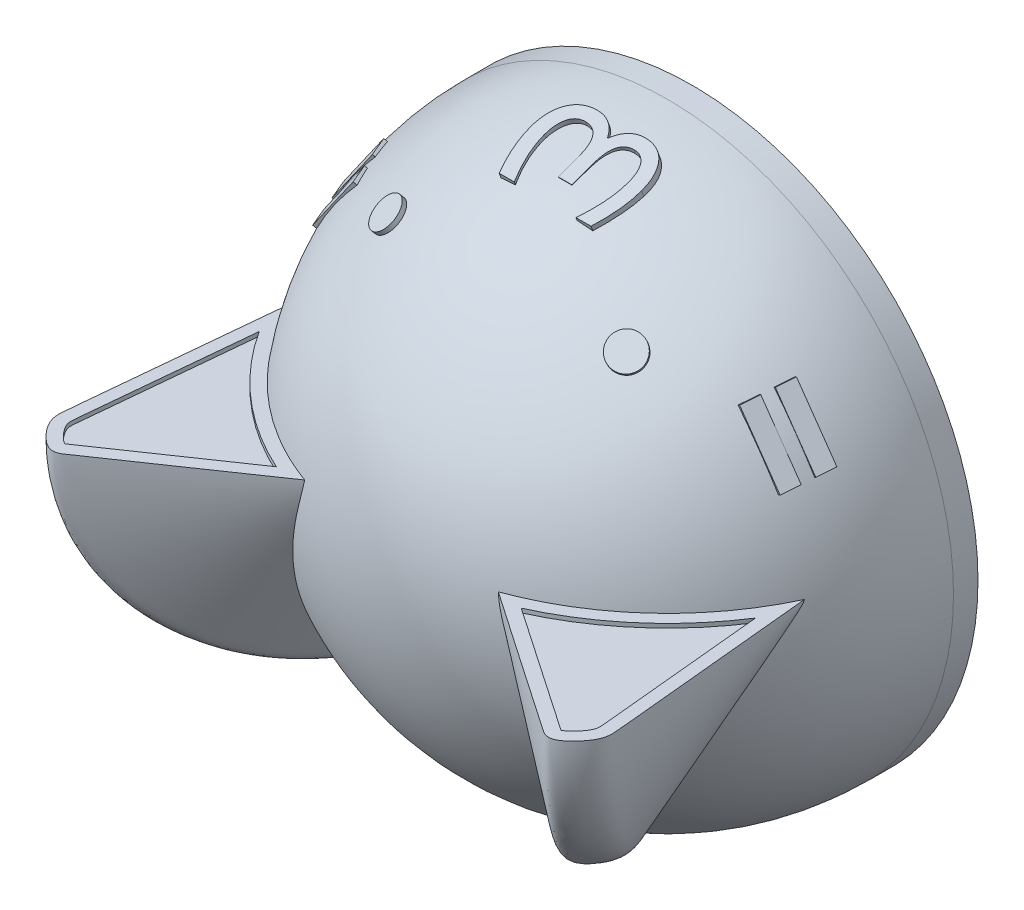
SolidWorks part; units mm, degrees
ref_plane "Front Plane" through (0, 0, 0) normal (0, 0, 1) x (1, 0, 0)
ref_plane "Top Plane" through (0, 0, 0) normal (0, 1, 0) x (1, 0, 0)
ref_plane "Right Plane" through (0, 0, 0) normal (1, 0, 0) x (0, 0, -1)
sketch "Sketch2" plane through (0, 0, 0) normal (0, 0, 1) x (1, 0, 0)
  circle A0 centre (0, 0) radius 70
  dimension "D1" = 140
sketch "Sketch1" plane through (0, 0, 0) normal (0, 0, 1) x (1, 0, 0)
  line L8 (48.8765, 46.4076) -> (-48.8765, 46.4076)
  line L9 (-48.8765, 46.4076) -> (-48.8765, -28.5347)
  line L10 (-48.8765, -28.5347) -> (48.8765, -28.5347)
  line L11 (48.8765, -28.5347) -> (48.8765, 46.4076)
  line L12 (48.8765, 46.4076) -> (-48.8765, 46.4076)
  line L13 (-48.8765, 46.4076) -> (-48.8765, -28.5347)
  line L14 (-48.8765, -28.5347) -> (48.8765, -28.5347)
  line L15 (48.8765, -28.5347) -> (48.8765, 46.4076)
  dimension "D2" = 2.75
extrude "Boss-Extrude1" add sketch "Sketch2" along normal blind 6
extrude "Cut-Extrude1" cut sketch "Sketch1" along normal blind 5
dome "Dome1" faces to dome 1 distance 70 reverse direction no elliptical dome no face at (70, 0, 6) parameters "D1"=70
ref_plane "Plane1" through (0, 10, 0) normal (0, 1, 0) x (1, 0, 0)
sketch "Sketch6" plane through (0, 10, 0) normal (0, 1, 0) x (1, 0, 0)
  line L0 (-62.7908, -35.2799) -> (-69.282, -102.407) construction
  line L2 (70, -6) -> (-70, -6) construction
  line L3 (-69.282, -102.407) -> (-23.6959, -71.1038) construction
  line L4 (-62.7908, -35.2799) -> (0, -6) construction
  line L5 (0, -6) -> (-23.6959, -71.1038) construction
  line L6 (0, -6) -> (0, 0) construction
  arc A0 (-69.282, -6) -> (69.282, -6) centre (0, -6) ccw
  arc A1 (-69.282, -6) -> (69.282, -6) centre (0, -6) ccw construction
  arc A2 (-62.7908, -35.2799) -> (-23.6959, -71.1038) centre (0, -6) ccw
  spline S0 degree 3 poles (-62.7908, -35.2799) (-64.4136, -52.0616) (-66.0364, -68.8434) (-67.6592, -85.6252) (-67.801, -87.0913) (-68.0846, -90.0236) (-61.5282, -97.0826) (-59.0997, -95.415) (-57.8855, -94.5812) (-46.4889, -86.7554) (-35.0924, -78.9296) (-23.6959, -71.1038) knots 0 0 0 0 0.480293 0.480293 0.480293 0.522253 0.564213 0.606173 0.606173 0.606173 1 1 1 1
  dimension "D2" = 50
  dimension "D3" = 20
  dimension "D4" = 45
ref_axis "Axis1" through (-69.282, 10, 102.407) along (0.5836, 0, -0.8121)
ref_plane "Plane2" through (2.8434, 0, 2.0434) normal (0.8121, 0, 0.5836) x (0.3406, -0.8121, -0.4739)
sketch "Sketch7" plane through (2.8434, 0, 2.0434) normal (0.8121, 0, 0.5836) x (0.3406, -0.8121, -0.4739)
  line L0 (-46.2239, -47.1856) -> (-74.5562, -86.6104) construction
  line L1 (-46.2239, -47.1856) -> (-74.5562, -86.6104) construction
  line L2 (12.6309, 34.7118) -> (-51.3954, -54.3818) construction
  line L3 (-46.2239, -47.1856) -> (-74.5562, -86.6104) construction
  arc A0 (-59.6874, 36.8938) -> (54.0006, -44.8071) centre (-2.8434, -3.9566) ccw
  arc A1 (-59.6874, 36.8938) -> (54.0006, -44.8071) centre (-2.8434, -3.9566) ccw construction
  arc A2 (-74.5562, -86.6104) -> (-3.9128, -73.9485) centre (-45.3773, -46.0075) ccw
  arc A3 (-59.6874, 36.8938) -> (54.0006, -44.8071) centre (-2.8434, -3.9566) ccw construction
  dimension "D1" = 50
sweep "Sweep1" add profiles "Sketch6" path "Sketch7"
mirror "Mirror1" about plane through (0, 0, 0) normal (1, 0, 0) of "Sweep1"
sketch "Sketch8" plane through (0, 10, 0) normal (0, 1, 0) x (1, 0, 0)
  line L0 (-60.7052, -92.783) -> (-29.9727, -71.7748)
  arc A2 (-60.7352, -45.1908) -> (-29.9727, -71.7748) centre (0, -6) ccw
  arc A3 (-60.7352, -45.1908) -> (-29.9727, -71.7748) centre (0, -6) ccw
  spline S2 degree 3 poles (228.0161, 2940.8674) (130.9731, 1937.3188) (33.5339, 929.6722) (-64.0045, -78.9989) (-64.5246, -84.3774) (-64.6484, -85.658) (-64.6979, -86.1702) (-64.7231, -86.4263) (-64.7569, -86.9394) (-64.7656, -87.1964) (-64.7356, -87.7127) (-64.6944, -87.9682) (-64.4849, -88.7007) (-64.2349, -89.1595) (-63.6777, -90.016) (-63.3673, -90.4201) (-62.7014, -91.1945) (-62.3441, -91.5657) (-61.7717, -92.0782) (-61.5747, -92.2419) (-61.2636, -92.4698) (-61.1577, -92.5426) (-60.9941, -92.6432) (-60.9387, -92.6753) (-57.0734, -94.7057) (-50.633, -92.1765) (1454.5839, 2489.9947) knots -60.722746 -60.722746 -60.722746 -60.722746 0.5 0.75 0.8125 0.828125 0.828125 0.84375 0.84375 0.859375 0.859375 0.875 0.875 0.90625 0.90625 0.9375 0.9375 0.96875 0.96875 0.984375 0.984375 0.992188 0.992188 0.996094 0.996094 1.25844 1.25844 1.25844 1.25844 only from (-60.7352, -45.1908) to (-60.7052, -92.783)
  spline S3 degree 3 poles (-60.7352, -45.1908) (-61.5278, -53.3867) (-62.7166, -65.6805) (-64.0045, -78.9989) (-64.5246, -84.3774) (-64.6484, -85.658) (-64.6979, -86.1702) (-64.7231, -86.4263) (-64.7569, -86.9394) (-64.7656, -87.1964) (-64.7356, -87.7127) (-64.6944, -87.9682) (-64.4849, -88.7007) (-64.2349, -89.1595) (-63.6777, -90.016) (-63.3673, -90.4201) (-62.7014, -91.1945) (-62.3441, -91.5657) (-61.7717, -92.0782) (-61.5747, -92.2419) (-61.2636, -92.4698) (-61.1577, -92.5426) (-60.9941, -92.6432) (-60.9387, -92.6753) (-60.8253, -92.7349) (-60.768, -92.7637) (-60.7052, -92.783) knots 0 0 0 0 0.5 0.75 0.8125 0.828125 0.828125 0.84375 0.84375 0.859375 0.859375 0.875 0.875 0.90625 0.90625 0.9375 0.9375 0.96875 0.96875 0.984375 0.984375 0.992188 0.992188 0.996094 0.996094 1 1 1 1
  dimension "D1" = 3
extrude "Cut-Extrude2" cut sketch "Sketch8" against normal blind 1
mirror "Mirror2" about plane through (0, 0, 0) normal (1, 0, 0) of "Cut-Extrude2"
ref_plane "Plane3" through (0, 0, 45) normal (0, 0, -1) x (-1, 0, 0)
sketch "Sketch9" plane through (0, 0, 45) normal (0, 0, -1) x (-1, 0, 0)
  line L0 (0, 0) -> (0, 58.1292) construction
  line L1 (0, 0) -> (29.0646, 50.3413) construction
  arc A0 (57.2626, 10) -> (-57.2626, 10) centre (0, 0) ccw
  arc A1 (-57.6814, -7.2011) -> (57.6814, -7.2011) centre (0, 0) ccw
  arc A2 (-57.6814, -7.2011) -> (57.6814, -7.2011) centre (0, 0) ccw construction
  arc A3 (57.2626, 10) -> (-57.2626, 10) centre (0, 0) ccw construction
  dimension "D1" = 30
ref_plane "Plane4" through (-29.0646, 50.3413, 45) normal (-0.4152, 0.7192, 0.5571) x (0.9097, 0.3314, 0.2502)
sketch "Sketch10" plane through (-29.0646, 50.3413, 45) normal (-0.4152, 0.7192, 0.5571) x (0.9097, 0.3314, 0.2502)
  circle A0 centre (0, 0) radius 4
  point P0 (0, 0)
  dimension "D1" = 8
extrude "Boss-Extrude2" add sketch "Sketch10" against normal blind 1 and the other way blind 1 contours A0
mirror "Mirror3" about plane through (0, 0, 0) normal (1, 0, 0) of "Boss-Extrude2"
ref_plane "Plane5" through (0, 0, 30) normal (0, 0, -1) x (-1, 0, 0)
sketch "Sketch11" plane through (0, 0, 30) normal (0, 0, -1) x (-1, 0, 0)
  line L0 (0, 0) -> (0, 65.7571)
  line L1 (0, 0) -> (53.8651, 37.7167)
  circle A0 centre (0, 0) radius 65.7571
  circle A1 centre (0, 0) radius 65.7571
  dimension "D1" = 55
ref_plane "Plane6" through (0, 65.7571, 30) normal (0, 0.9394, 0.3429) x (1, 0, 0)
sketch "Sketch13" plane through (0, 65.7571, 30) normal (0, 0.9394, 0.3429) x (1, 0, 0)
  line L1 (-20.6544, -1.8637) -> (20.6544, -1.8637) construction
  line L2 (-20.6544, -1.8637) -> (-20.6544, 13.1363) construction
  line L3 (-20.6544, 13.1363) -> (20.6544, 13.1363) construction
  line L4 (20.6544, -1.8637) -> (20.6544, 13.1363) construction
  line L5 (-20.6544, -1.8637) -> (20.6544, 13.1363) construction
  line L6 (-20.6544, 13.1363) -> (20.6544, -1.8637) construction
  text T0 "ω" font "@Microsoft YaHei" height in points 96
  point P0 (0, 5.6363)
  dimension "D1" = 15
extrude "Boss-Extrude3" add sketch "Sketch13" along normal blind 0.1 and the other way blind 2
ref_plane "Plane7" through (-53.8651, 37.7167, 30) normal (-0.7695, 0.5388, 0.3429) x (0.2809, -0.1967, 0.9394)
sketch "Sketch15" plane through (-53.8651, 37.7167, 30) normal (-0.7695, 0.5388, 0.3429) x (0.2809, -0.1967, 0.9394)
  line L1 (-12.2488, -19.3346) -> (12.2488, -19.3346) construction
  line L2 (-12.2488, -19.3346) -> (-12.2488, 19.3346) construction
  line L3 (-12.2488, 19.3346) -> (12.2488, 19.3346) construction
  line L4 (12.2488, -19.3346) -> (12.2488, 19.3346) construction
  line L5 (-12.2488, -19.3346) -> (12.2488, 19.3346) construction
  line L6 (-12.2488, 19.3346) -> (12.2488, -19.3346) construction
  text T0 "=" font "Century Gothic" height in points 96
  point P0 (0, 0)
  point P1 (0, 0)
extrude "Boss-Extrude4" add sketch "Sketch15" along normal blind 0.1 and the other way blind 2
mirror "Mirror4" about plane through (0, 0, 0) normal (1, 0, 0) of "Boss-Extrude4"
sketch "Sketch16" plane through (0, 0, 0) normal (0, 0, -1) x (-1, 0, 0)
  line L0 (0, 70) -> (0, -70) construction
  circle A0 centre (0, 0) radius 70 construction
  point P0 (0, 70)
